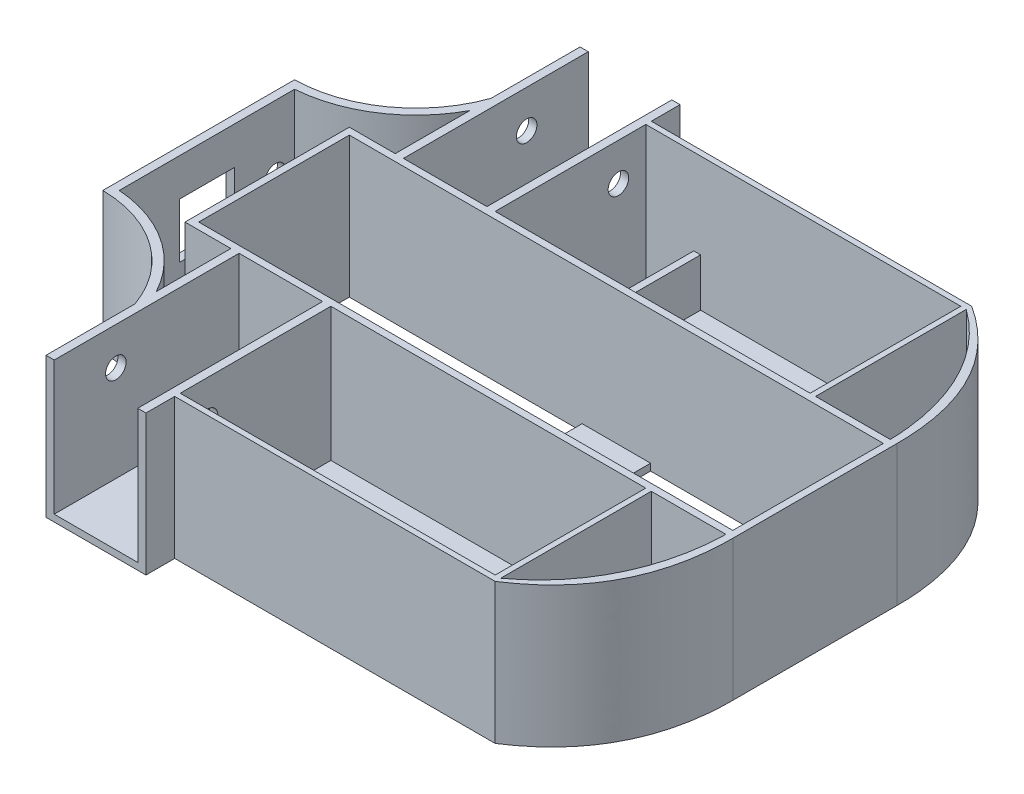
SolidWorks part; units mm, degrees
ref_plane "Спереди" through (0, 0, 0) normal (0, 0, 1) x (1, 0, 0)
ref_plane "Сверху" through (0, 0, 0) normal (0, 1, 0) x (1, 0, 0)
ref_plane "Справа" through (0, 0, 0) normal (1, 0, 0) x (0, 0, -1)
other "Configuration Table"
sketch "Эскиз2" plane through (0, 0, 0) normal (0, 1, 0) x (1, 0, 0)
  line L0 (76.0744, 0) -> (-76.0744, 0) construction
  line L1 (0, 70.3818) -> (0, -70.3818) construction
  line L2 (39, -11) -> (-39, -11)
  line L3 (-39, 11) -> (-39, -11)
  line L4 (40, -12) -> (-40, -12)
  line L5 (-40, 12) -> (-40, -12)
  line L6 (40, 12) -> (-40, 12)
  line L7 (39, 11) -> (-39, 11)
  line L8 (40, 12) -> (40, -12)
  line L9 (39, 11) -> (39, -11)
  line L10 (-50, 14) -> (-50, -14)
  line L11 (-32.1, -12) -> (-32.1, -39)
  line L12 (-33.3, -39) -> (-33.3, -26)
  line L13 (-26, 42.2286) -> (-26, -42.2286) construction
  line L14 (-33.3, -12) -> (-33.3, -22.9039)
  line L15 (-48.8, 12.8) -> (-48.8, -12.8)
  line L16 (-19.9, -12) -> (-19.9, -39)
  line L17 (-18.7, -39) -> (-33.3, -39)
  line L18 (-18.7, -39) -> (-18.7, -12)
  line L19 (-33.3, 39) -> (-33.3, 26)
  line L20 (-18.7, 34) -> (27.3, 34)
  line L21 (-33.3, 12) -> (-33.3, 22.9039)
  line L22 (27.3, 34) -> (27.3, 12)
  line L23 (-32.1, 12) -> (-32.1, 39)
  line L24 (-18.7, 39) -> (-33.3, 39)
  line L25 (-19.9, 12) -> (-19.9, 39)
  line L26 (-18.7, 39) -> (-18.7, 12)
  line L27 (28.1, 12) -> (28.1, 34.8)
  line L28 (28.1, 34.8) -> (-18.7, 34.8)
  line L29 (28.1, -12) -> (28.1, -34.8)
  line L30 (27.3, -34) -> (27.3, -12)
  line L31 (-18.7, -34) -> (27.3, -34)
  line L32 (28.1, -34.8) -> (-18.7, -34.8)
  line L33 (-15.7, 31) -> (-15.7, 16) construction
  line L34 (-5, 11) -> (-5, -11)
  line L35 (5, 11) -> (5, -11)
  line L36 (-13.7, 23.5) -> (-17.7, 23.5) construction
  line L37 (-13.7, 27.5) -> (-17.7, 27.5)
  line L38 (-13.7, 19.5) -> (-17.7, 19.5)
  line L39 (-17.7, 27.5) -> (-17.7, 19.5)
  line L40 (-13.7, 27.5) -> (-13.7, 19.5)
  line L41 (-10.7, 34) -> (-10.7, 12)
  line L42 (-11.7, 34) -> (-11.7, 12)
  arc A0 (-50, -14) -> (-33.3, -26) centre (-50.2713, -31.998) cw
  arc A1 (-48.8, -12.8) -> (-33.3, -22.9039) centre (-50.2713, -31.998) cw
  circle A2 centre (0, 0) radius 1.5
  arc A3 (-50, 14) -> (-33.3, 26) centre (-50.2713, 31.998) ccw
  arc A4 (-48.8, 12.8) -> (-33.3, 22.9039) centre (-50.2713, 31.998) ccw
  circle A5 centre (-15.7, 16) radius 1.5
  circle A6 centre (-15.7, 31) radius 1.5
  circle A7 centre (24.1, 23) radius 2
  circle A8 centre (24.1, -23) radius 2
  spline S0 degree 2 poles (28.1, 34.8) (40.0183, 27.0874) (40, 12) knots 0 0 0 1 1 1
  spline S1 degree 3 poles (28.1, 34) (35.6673, 28.51) (38.8306, 20.078) (39, 12) knots 0 0 0 0 1 1 1 1
  spline S2 degree 2 poles (28.1, -34.8) (40.0183, -27.0874) (40, -12) knots 0 0 0 1 1 1
  spline S3 degree 3 poles (28.1, -34) (35.6673, -28.51) (38.8306, -20.078) (39, -12) knots 0 0 0 0 1 1 1 1
  point P4 (0, 0)
  point P8 (0, 0)
  point P11 (0, -11)
  point P14 (-39, 0)
  point P16 (0, -12)
  point P19 (-40, 0)
  point P23 (-50, 0)
  point P29 (-26, 0)
  point P34 (-48.8, 0)
  point P79 (-15.7, 23.5)
  point P80 (-15.7, 23.5)
  point P83 (-15.7, 27.5)
  dimension "D12" = 18
  dimension "D14" = 3
  dimension "D28" = 4
  dimension "D1" = 39
  dimension "D2" = 11
  dimension "D3" = 1
  dimension "D4" = 1
  dimension "D6" = 10
  dimension "D5" = 14
  dimension "D8" = 1.2
  dimension "D10" = 6.1
  dimension "D7" = 26
  dimension "D11" = 14
  dimension "D9" = 27
  dimension "D13" = 1.2
  dimension "D16" = 1.2
  dimension "D15" = 46
  dimension "D17" = 22
  dimension "D18" = 0.8
  dimension "D19" = 0.8
  dimension "D20" = 5
  dimension "D21" = 4
  dimension "D22" = 15
  dimension "D23" = 3
  dimension "D25" = 4
  dimension "D26" = 4
  dimension "D24" = 38
  dimension "D27" = 1
  dimension "D29" = 23
  dimension "D30" = 4
extrude "Стенки" add sketch "Эскиз2" along normal blind 20.5 contours L8 L6 L5 L4 L7 L9 L2 L3 | L15 A4 L21 L6 L23 L24 L19 A3 L10 A0 L12 L17 L11 L4 L14 A1 | L26 L24 L25 L6 | L17 L18 L4 L16 | L27 L28 L26 L20 L22 L6 | L27 S1 L6 S0 | L32 L29 L4 L30 L31 L18 | S3 L29 S2 L4 region at (36.9137, 0, 24.9161) region at (39.5, 0, 11.1648) region at (39.5, 0, -12.2572) region at (4.7, 0, 34.2794) region at (27.5794, 0, -34.4) region at (-19.3, 0, 25.5) region at (-19.3, 0, -25.5) region at (-32.7, 0, 38.1997)
extrude "Дно" add sketch "Эскиз2<3>" along normal blind 1 contours L17 L16 L4 L11 | L6 L25 L24 L23 | A4 L15 A1 L14 L4 L5 L6 L21 | L35 L7 L34 L2 A2 | L20 L26 L6 L22 | L18 L31 L30 L4 | L20 L41 L6 L22 | L42 L20 L26 L6 A6 A5 L37 L40 L38 L39 | L20 L42 L6 L41 region at (0, 0, 10.7583) region at (4.051, 0, 23) region at (8.0589, 0, -23) region at (-15.2, 0, -33.7691) region at (-26, 0, 25.5) region at (-11.2, 0, -23) region at (-26, 0, -25.5) region at (-42.0509, 0, 0)
sketch "Эскиз2<3>" plane through (0, 0, 0) normal (0, 1, 0) x (1, 0, 0) same geometry as "Эскиз2"
sketch "Эскиз3" plane through (0, 0, 0) normal (1, 0, 0) x (0, 0, -1)
  line L0 (0, -31.3592) -> (0, 31.3592) construction
  line L1 (4, 15) -> (-4, 15)
  line L2 (52.0909, 0) -> (-52.0909, 0) construction
  line L3 (12, 31.3592) -> (12, -12.1141) construction
  line L4 (10, 11) -> (-10, 11) construction
  line L5 (-4, 15) -> (-4, 7)
  line L6 (4, 15) -> (4, 7)
  line L7 (4, 7) -> (-4, 7)
  circle A0 centre (30, 15) radius 1.5
  circle A1 centre (-30, 15) radius 1.5
  circle A2 centre (-10, 11) radius 1.5
  circle A3 centre (10, 11) radius 1.5
  point P4 (0, 0)
  point P8 (0, 0)
  point P20 (0, 11)
  point P22 (0, 15)
  point P25 (-4, 11)
  point P26 (4, 11)
  dimension "D1" = 3
  dimension "D5" = 4
  dimension "D2" = 18
  dimension "D3" = 15
  dimension "D4" = 20
  dimension "D6" = 8
  dimension "D7" = 11
extrude "Вырез-Вытянуть1" cut sketch "Эскиз3" against normal up to surface (33.3 mm away) from surface contours A1 | A0 region at (0, 15, -30) region at (0, 15, 30) up to face at (-33.3, 10.25, -32.5) starting at face at (-18.7, 10.75, -23)
extrude "Вырез-Вытянуть2" cut sketch "Эскиз3<2>" against normal up to surface (50 mm away) from surface up to face at (-50, 10.25, 0) starting at face at (-48.8, 10.75, 0)
sketch "Эскиз3<2>" plane through (0, 0, 0) normal (1, 0, 0) x (0, 0, -1) same geometry as "Эскиз3"
extrude "Бобышка-Вытянуть4" add sketch "Эскиз2<5>" along normal blind 8 contours L20 L42 L6 L41 region at (-11.2, 0, -23)
sketch "Эскиз2<5>" plane through (0, 0, 0) normal (0, 1, 0) x (1, 0, 0) same geometry as "Эскиз2"
equation "\"D1@Эскиз2\"=39"
